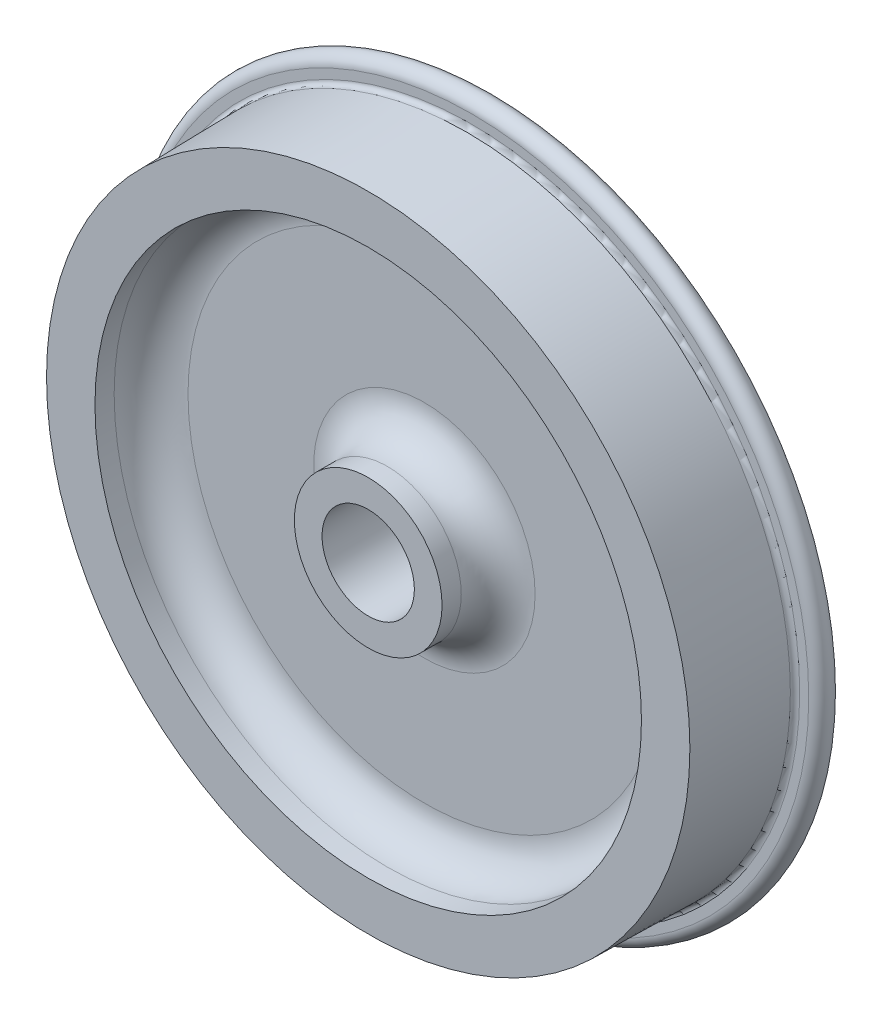
SolidWorks part; units mm, degrees
material "Gray Cast Iron"
ref_plane "Front Plane" through (0, 0, 0) normal (0, 0, 1) x (1, 0, 0)
ref_plane "Top Plane" through (0, 0, 0) normal (0, 1, 0) x (1, 0, 0)
ref_plane "Right Plane" through (0, 0, 0) normal (1, 0, 0) x (0, 0, -1)
sketch "Sketch1" plane through (0, 0, 0) normal (0, 0, 1) x (1, 0, 0)
  circle A0 centre (0, 0) radius 58.42
  dimension "D1" = 116.84
extrude "Boss-Extrude1" add sketch "Sketch1" along normal blind 13.97
sketch "Sketch2" plane through (0, 0, 13.97) normal (0, 0, 1) x (1, 0, 0)
  circle A0 centre (0, 0) radius 12.7
  circle A1 centre (0, 0) radius 46.99
  dimension "D1" = 25.4
  dimension "D2" = 93.98
extrude "Cut-Extrude1" cut sketch "Sketch2" against normal blind 9.652
fillet "Fillet1" radius 6.35 2 edges at (12.7, 0, 4.318) (46.99, 0, 4.318)
sketch "Sketch3" plane through (0, 0, 0) normal (0, 0, -1) x (-1, 0, 0)
  circle A0 centre (0, 0) radius 60.96
  dimension "D1" = 121.92
extrude "Boss-Extrude2" add sketch "Sketch3" along normal blind 7.62
sketch "Sketch4" plane through (0, 0, 13.97) normal (0, 0, 1) x (1, 0, 0)
  circle A0 centre (0, 0) radius 7.9375
  dimension "D1" = 15.875
extrude "Cut-Extrude2" cut sketch "Sketch4" against normal through all
sketch "Sketch5" plane through (0, 0, 0) normal (0, 0, 1) x (1, 0, 0)
  circle A0 centre (0, 0) radius 60.96 construction
  circle A1 centre (0, 0) radius 60.96
  circle A2 centre (0, 0) radius 58.42 construction
  circle A3 centre (0, 0) radius 58.42
extrude "FlangeWidthMachined" cut sketch "Sketch5" against normal blind 3.81
sketch "Sketch7" plane through (0, 0, 13.97) normal (0, 0, 1) x (1, 0, 0)
  circle A0 centre (0, 0) radius 58.42 construction
  circle A1 centre (0, 0) radius 58.42
  circle A2 centre (0, 0) radius 55.5625
  dimension "D1" = 111.125
extrude "Cut-Extrude5" cut sketch "Sketch7" against normal up to surface (17.78 mm away) up to face at (58.42, 0, -3.81)
sketch "Sketch6" plane through (0, 0, -3.81) normal (0, 0, 1) x (1, 0, 0)
  circle A1 centre (0, 0) radius 55.5625 construction
  circle A2 centre (0, 0) radius 59.8805
  circle A3 centre (0, 0) radius 60.96 construction
  circle A4 centre (0, 0) radius 60.96
  circle A6 centre (0, 0) radius 55.5625 construction
  dimension "D1" = 4.318
extrude "Flange Depth Machined" cut sketch "Sketch6" against normal through all
draft "Draft1" type of draft neutral plane draft angle 1 neutral plane "Front Plane" faces to draft 1 face at (55.5625, 0, -3.81) neutral plane through (0, 0, 0) neutral plane normal (0, 0, 1) parameters "D1"=1
fillet "Fillet2" radius 0.8128 1 edges at (55.629, 0, -3.81)
fillet "Fillet3" 2 edges at (59.8805, 0, -7.62) (59.8805, 0, -3.81) type full round first side face at (7.9375, 0, -7.62) second side face at (56.4277, 0, -3.81) middle face at (59.8805, 0, -7.62)
